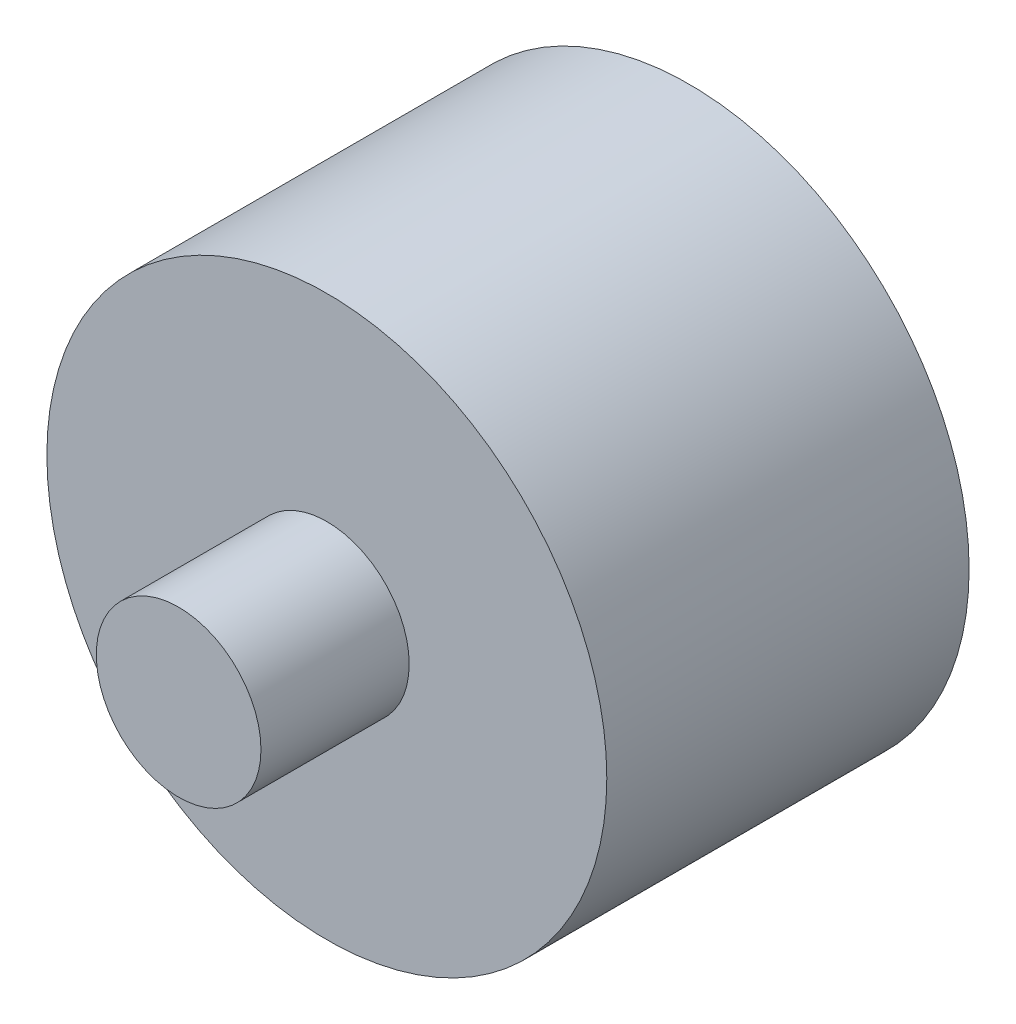
SolidWorks part; units mm, degrees
ref_plane "Ön Düzlem" through (0, 0, 0) normal (0, 0, 1) x (1, 0, 0)
ref_plane "Üst Düzlem" through (0, 0, 0) normal (0, 1, 0) x (1, 0, 0)
ref_plane "Sağ Düzlem" through (0, 0, 0) normal (1, 0, 0) x (0, 0, -1)
sketch "Çizim1" plane through (0, 0, 0) normal (0, 0, 1) x (1, 0, 0)
  circle A0 centre (0, 0) radius 5
  circle A1 centre (0, 0) radius 17
  dimension "D1" = 10
  dimension "D2" = 34
extrude "Yükseklik-Ekstrüzyon1" add sketch "Çizim1" along normal blind 22 contours A0 | A1 A0 region at (0, 0, 0) region at (-16.5192, 0, 0)
extrude "Yükseklik-Ekstrüzyon2" add sketch "Çizim1<3>" along normal blind 31 contours A0 region at (0, 0, 0)
sketch "Çizim1<3>" plane through (0, 0, 0) normal (0, 0, 1) x (1, 0, 0) same geometry as "Çizim1"
